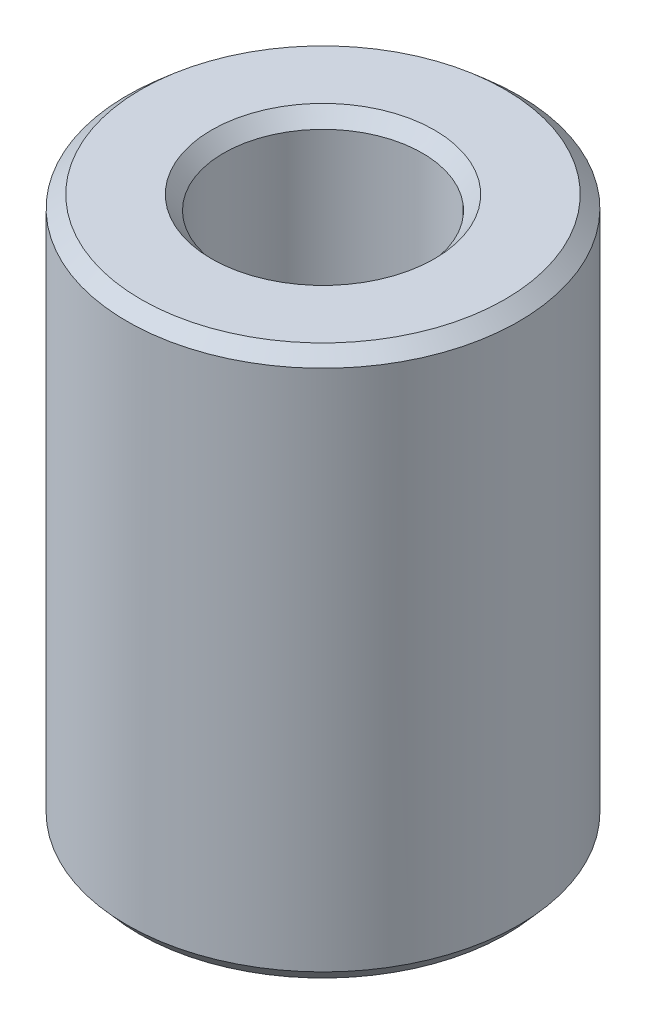
SolidWorks part; units mm, degrees
ref_plane "Front Plane" through (0, 0, 0) normal (0, 0, 1) x (1, 0, 0)
ref_plane "Top Plane" through (0, 0, 0) normal (0, 1, 0) x (1, 0, 0)
ref_plane "Right Plane" through (0, 0, 0) normal (1, 0, 0) x (0, 0, -1)
sketch "Sketch1" plane through (0, 0, 0) normal (0, 1, 0) x (1, 0, 0)
  circle A0 centre (0, 0) radius 45
  dimension "SLEEVE_OD" = 90
extrude "Boss-Extrude1" add sketch "Sketch1" along normal blind 126.1222
sketch "Sketch2" plane through (0, 0, 0) normal (0, 1, 0) x (1, 0, 0)
  circle A0 centre (0, 0) radius 22.8426
  dimension "BORE_D" = 45.6851
extrude "Cut-Extrude1" cut sketch "Sketch2" along normal through all
chamfer "Chamfer1" distance 2.7894 angle 48.835 4 edges at (0, 126.1222, 22.8426) (0, 0, 22.8426) (0, 0, 45) (0, 126.1222, 45) first distance on face at (0, 126.1222, 22.8426) first distance on face at (0, 0, 22.8426) first distance on face at (0, 126.1222, 45)
